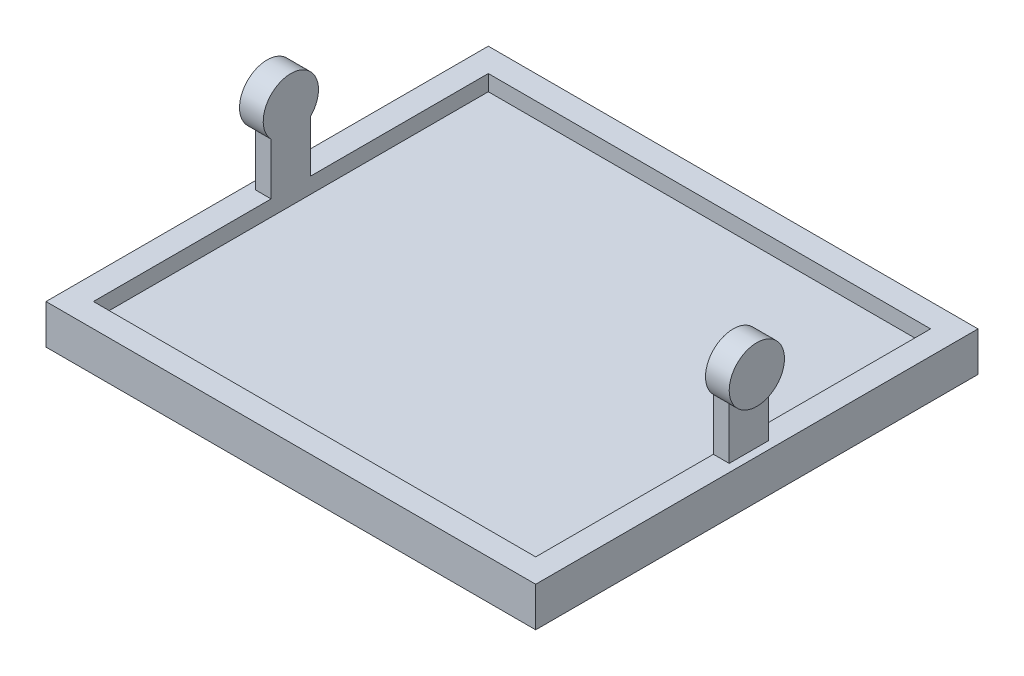
SolidWorks part; units mm, degrees
ref_plane "Front" through (0, 0, 0) normal (0, 0, 1) x (1, 0, 0)
ref_plane "Top" through (0, 0, 0) normal (0, 1, 0) x (1, 0, 0)
ref_plane "Right" through (0, 0, 0) normal (1, 0, 0) x (0, 0, -1)
sketch "Sketch1" plane through (0, 0, 0) normal (0, 1, 0) x (1, 0, 0)
  line L1 (-35.56, 31.75) -> (35.56, 31.75)
  line L2 (-35.56, 31.75) -> (-35.56, -31.75)
  line L3 (-35.56, -31.75) -> (35.56, -31.75)
  line L4 (35.56, 31.75) -> (35.56, -31.75)
  line L5 (-35.56, 31.75) -> (35.56, -31.75) construction
  line L6 (-35.56, -31.75) -> (35.56, 31.75) construction
  line L7 (-39.37, 35.56) -> (39.37, 35.56)
  line L8 (-39.37, 35.56) -> (-39.37, -35.56)
  line L9 (-39.37, -35.56) -> (39.37, -35.56)
  line L10 (39.37, 35.56) -> (39.37, -35.56)
  line L11 (-39.37, 35.56) -> (39.37, -35.56) construction
  line L12 (-39.37, -35.56) -> (39.37, 35.56) construction
  point P0 (0, 0)
  point P6 (0, 0)
  point P11 (0, 0)
  dimension "D1" = 71.12
  dimension "D2" = 63.5
  dimension "D3" = 78.74
  dimension "D4" = 71.12
extrude "inner-lid" add sketch "Sketch1" along normal blind 3.81 contours L2 L1 L4 L3
extrude "outer-lid" add sketch "Sketch1<5>" along normal blind 6.35
sketch "Sketch1<5>" plane through (0, 0, 0) normal (0, 1, 0) x (1, 0, 0) same geometry as "Sketch1"
sketch "Sketch2" plane through (0, 6.35, 0) normal (0, 1, 0) x (1, 0, 0)
  line L0 (35.56, 3.175) -> (38.1, 3.175)
  line L1 (35.56, 3.175) -> (35.56, -3.175)
  line L6 (-38.1, 3.175) -> (-35.56, 3.175)
  line L7 (-38.1, 3.175) -> (-38.1, -3.175)
  line L8 (-38.1, -3.175) -> (-35.56, -3.175)
  line L9 (-35.56, 3.175) -> (-35.56, -3.175)
  line L10 (-38.1, 3.175) -> (-35.56, -3.175) construction
  line L11 (-38.1, -3.175) -> (-35.56, 3.175) construction
  line L12 (-35.56, 31.75) -> (-35.56, -31.75) construction
  line L13 (-39.37, -35.56) -> (39.37, -35.56) construction
  line L14 (35.56, -3.175) -> (38.1, -3.175)
  line L15 (38.1, 3.175) -> (38.1, -3.175)
  line L16 (35.56, 3.175) -> (38.1, -3.175) construction
  line L17 (35.56, -3.175) -> (38.1, 3.175) construction
  line L18 (35.56, -31.75) -> (35.56, 31.75) construction
  point P0 (-36.83, 0)
  point P5 (0, 0)
  point P6 (0, 0)
  point P7 (-36.83, -1.1401)
  point P10 (36.83, 0)
  dimension "D1" = 2.54
  dimension "D2" = 6.35
  dimension "D3" = 35.56
  dimension "D4" = 35.56
  dimension "D5" = 6.35
  dimension "D6" = 2.54
extrude "hole-slides" add sketch "Sketch2" along normal blind 11.43
sketch "Sketch3" plane through (-35.56, 0, 0) normal (1, 0, 0) x (0, 0, -1)
  line L0 (-3.175, 17.78) -> (3.175, 17.78) construction
  circle A0 centre (0, 17.78) radius 4.445
  dimension "D1" = 8.89
extrude "hole-lid-1" add sketch "Sketch3" against normal up to vertex (3.81 mm away) up to point (-39.37, 6.35, 35.56)
sketch "Sketch4" plane through (35.56, 0, 0) normal (-1, 0, 0) x (0, 0, 1)
  line L0 (-3.175, 17.78) -> (3.175, 17.78) construction
  circle A0 centre (0, 17.78) radius 4.445
  dimension "D1" = 8.89
extrude "Boss-Extrude5" add sketch "Sketch4" against normal up to vertex (3.81 mm away) up to point (39.37, 6.35, 35.56)
